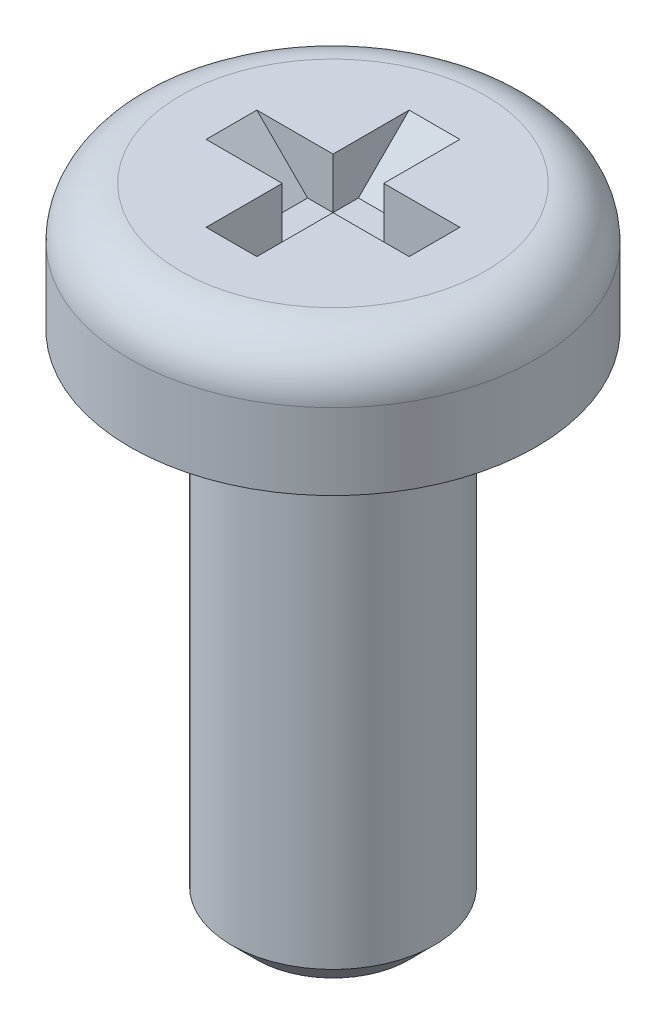
SolidWorks part; units mm, degrees
ref_plane "前视基准面" through (0, 0, 0) normal (0, 0, 1) x (1, 0, 0)
ref_plane "上视基准面" through (0, 0, 0) normal (0, 1, 0) x (1, 0, 0)
ref_plane "右视基准面" through (0, 0, 0) normal (1, 0, 0) x (0, 0, -1)
other "Configuration Table"
sketch "草图1" plane through (0, 0, 0) normal (0, 1, 0) x (1, 0, 0)
  circle A0 centre (0, 0) radius 2
  dimension "D1" = 4
extrude "凸台-拉伸1" add sketch "草图1" along normal blind 10
cosmetic thread "装饰螺纹线1" parameters "D2"=3
sketch "草图2" plane through (0, 10, 0) normal (0, 1, 0) x (1, 0, 0)
  circle A0 centre (0, 0) radius 4
  dimension "D1" = 8
extrude "凸台-拉伸2" add sketch "草图2" along normal blind 2.5
fillet "圆角1" radius 1 1 edges at (0, 12.5, 4)
chamfer "倒角1" distance 0.5 angle 45 1 edges at (0, 0, 2)
sketch "草图3" plane through (0, 12.5, 0) normal (0, 1, 0) x (1, 0, 0)
  line L0 (-2, 0) -> (2, 0)
  line L1 (0, 2) -> (0, -2)
  point P5 (0, 0)
  point P9 (0, 0)
  dimension "D1" = 4
  dimension "D2" = 4
extrude "切除-拉伸-薄壁1" cut sketch "草图3" against normal blind 1 thin thin type mid plane wall 1
chamfer "倒角2" distance 1 angle 45 4 edges at (0, 11.5, 2) (2, 11.5, 0) (0, 11.5, -2) (-2, 11.5, 0)
